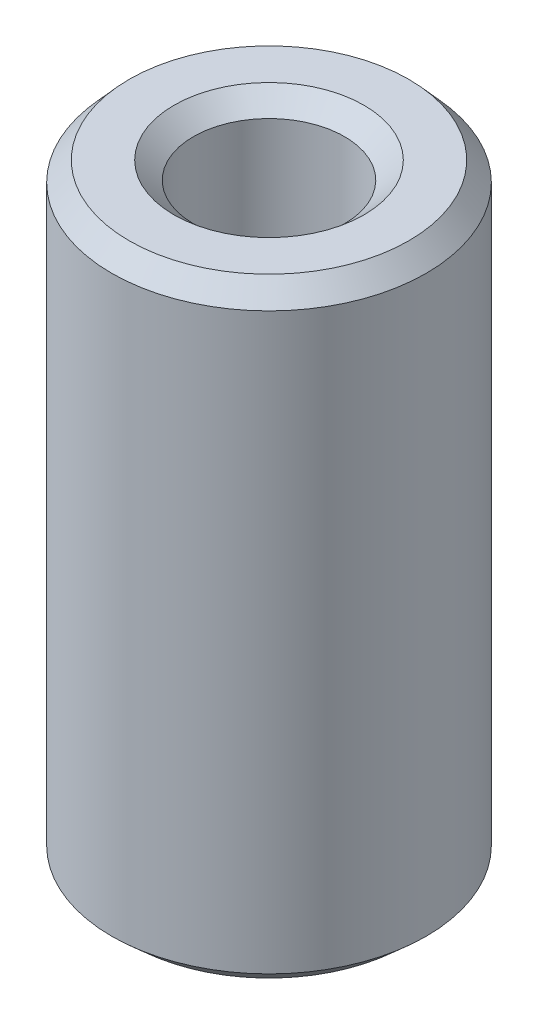
SolidWorks part; units mm, degrees
ref_plane "Front Plane" through (0, 0, 0) normal (0, 0, 1) x (1, 0, 0)
ref_plane "Top Plane" through (0, 0, 0) normal (0, 1, 0) x (1, 0, 0)
ref_plane "Right Plane" through (0, 0, 0) normal (1, 0, 0) x (0, 0, -1)
sketch "Sketch1" plane through (0, 0, 0) normal (0, 1, 0) x (1, 0, 0)
  circle A0 centre (0, 0) radius 15
  dimension "SLEEVE_OD" = 30
extrude "Boss-Extrude1" add sketch "Sketch1" along normal blind 58.2927
sketch "Sketch2" plane through (0, 0, 0) normal (0, 1, 0) x (1, 0, 0)
  circle A0 centre (0, 0) radius 7.2044
  dimension "BORE_D" = 14.4087
extrude "Cut-Extrude1" cut sketch "Sketch2" along normal through all
chamfer "Chamfer1" distance 1.8582 angle 41.787 4 edges at (0, 58.2927, 7.2044) (0, 0, 7.2044) (0, 0, 15) (0, 58.2927, 15) first distance on face at (0, 58.2927, 7.2044) first distance on face at (0, 0, 7.2044) first distance on face at (0, 58.2927, 15)
